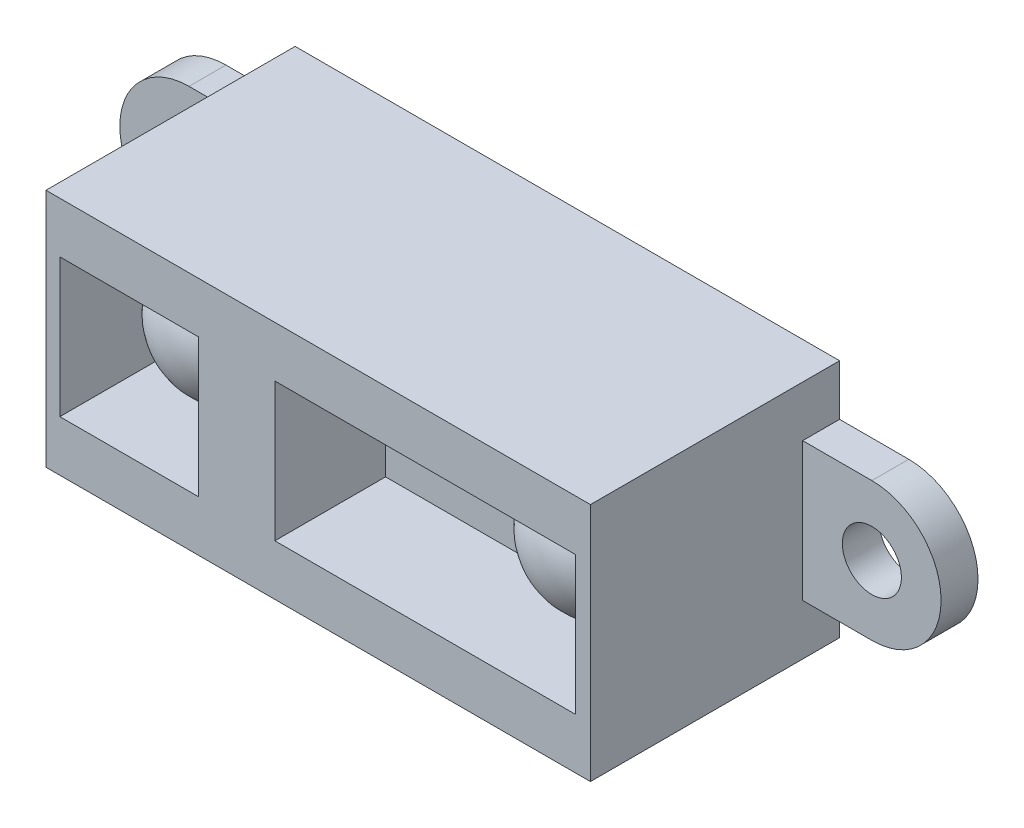
SolidWorks part; units mm, degrees
ref_plane "정면" through (0, 0, 0) normal (0, 0, 1) x (1, 0, 0)
ref_plane "윗면" through (0, 0, 0) normal (0, 1, 0) x (1, 0, 0)
ref_plane "우측면" through (0, 0, 0) normal (1, 0, 0) x (0, 0, -1)
sketch "스케치1" plane through (0, 0, 0) normal (0, 0, 1) x (1, 0, 0)
  line L1 (-14.75, -6.5) -> (14.75, -6.5)
  line L2 (-14.75, -6.5) -> (-14.75, 6.5)
  line L3 (-14.75, 6.5) -> (14.75, 6.5)
  line L4 (14.75, -6.5) -> (14.75, 6.5)
  line L5 (-14.75, -6.5) -> (14.75, 6.5) construction
  line L6 (-14.75, 6.5) -> (14.75, -6.5) construction
  point P0 (0, 0)
  dimension "D1" = 29.5
  dimension "D2" = 13
extrude "보스-돌출1" add sketch "스케치1" along normal blind 13.5
sketch "스케치2" plane through (0, 0, 0) normal (0, 0, -1) x (-1, 0, 0)
  line L1 (-18.5, -3.75) -> (18.5, -3.75)
  line L2 (-18.5, -3.75) -> (-18.5, 3.75)
  line L3 (-18.5, 3.75) -> (18.5, 3.75)
  line L4 (18.5, -3.75) -> (18.5, 3.75)
  line L5 (-18.5, -3.75) -> (18.5, 3.75) construction
  line L6 (-18.5, 3.75) -> (18.5, -3.75) construction
  circle A0 centre (-18.5, 0) radius 3.75
  circle A1 centre (18.5, 0) radius 3.75
  circle A2 centre (-18.5, 0) radius 1.6
  circle A3 centre (18.5, 0) radius 1.6
  point P0 (0, 0)
  line M1 (-14.75, 6.5) -> (-14.75, -6.5)
  line M3 (14.75, -6.5) -> (14.75, 6.5)
  dimension "D3" = 7.5
  dimension "D4" = 7.5
  dimension "D5" = 3.2
  dimension "D6" = 3.2
  dimension "D1" = 37
  dimension "D2" = 7.5
extrude "보스-돌출2" add sketch "스케치2" against normal blind 2 contours L3 L1 M1 M3 | A0 L3 M1 | A2 L2 A0 | A0 L1 M1 | A2 L2 A0 | A1 L3 M3 | A1 L1 M3 | A3 L4 A1 | A3 L4 A1 region at (15.5876, -2.9124, 0) region at (20.2946, 0, 0) region at (16.7054, 0, 0) region at (0, 0, 0) region at (15.5876, 2.9124, 0) region at (-15.5876, -2.9124, 0) region at (-16.7054, 0, 0) region at (-20.2946, 0, 0) region at (-15.5876, 2.9124, 0)
sketch "스케치3" plane through (0, 0, 13.5) normal (0, 0, 1) x (1, 0, 0)
  line L0 (-14.75, 6.5) -> (-14.75, -6.5) construction
  line L1 (-14, 3.75) -> (-6.5, 3.75)
  line L2 (-14, 3.75) -> (-14, -3.75)
  line L3 (-14, -3.75) -> (-6.5, -3.75)
  line L4 (-6.5, 3.75) -> (-6.5, -3.75)
  line L5 (14.75, 6.5) -> (-14.75, 6.5) construction
  line L7 (-2.35, 3.75) -> (13.95, 3.75)
  line L8 (-2.35, 3.75) -> (-2.35, -3.75)
  line L9 (-2.35, -3.75) -> (13.95, -3.75)
  line L10 (13.95, 3.75) -> (13.95, -3.75)
  dimension "D1" = 0.75
  dimension "D2" = 7.5
  dimension "7.5" = 7.5
  dimension "D4" = 2.75
  dimension "D5" = 4.15
  dimension "D6" = 16.3
extrude "컷-돌출1" cut sketch "스케치3" against normal blind 6
sketch "스케치4" plane through (0, 0, 7.5) normal (0, 0, 1) x (1, 0, 0)
  line L0 (-10.25, 3.75) -> (-10.25, -3.75)
  line L1 (-6.5, 3.75) -> (-14, 3.75) construction
  line L2 (-14, -3.75) -> (-6.5, -3.75) construction
  line L3 (13.95, 3.75) -> (-2.35, 3.75) construction
  line L4 (96.3285, 3.75) -> (96.3285, -3.75)
  arc A0 (-10.25, 3.75) -> (-10.25, -3.75) centre (-10.25, 0) ccw
  arc A1 (96.3285, 3.75) -> (96.3285, -3.75) centre (96.3285, 0) cw
revolve "회전1" add sketch "스케치4" angle 360 about L0 region at (-11.8415, 0, 7.5)
sketch "스케치6" plane through (0, 0, 7.5) normal (0, 0, 1) x (1, 0, 0)
  line L0 (9.9028, -3.75) -> (9.9028, 3.75)
  line L1 (-2.35, -3.75) -> (13.95, -3.75) construction
  line L2 (13.95, 3.75) -> (-2.35, 3.75) construction
  circle A0 centre (9.9028, 0) radius 3.75
revolve "회전14" add sketch "스케치6" angle 360 about L0 region at (11.4944, 0, 7.5)
sketch "스케치7" plane through (0, -6.5, 0) normal (0, -1, 0) x (1, 0, 0)
  line L0 (-14.75, 0) -> (14.75, 0) construction
  line L1 (-4.05, 0) -> (6.05, 0)
  line L2 (-4.05, 0) -> (-4.05, 3.3)
  line L3 (-4.05, 3.3) -> (6.05, 3.3)
  line L4 (6.05, 0) -> (6.05, 3.3)
  line L5 (-14.75, 13.5) -> (-14.75, 0) construction
  dimension "D1" = 3.3
  dimension "D2" = 10.1
  dimension "D3" = 10.7
extrude "보스-돌출3" add sketch "스케치7" along normal blind 6
